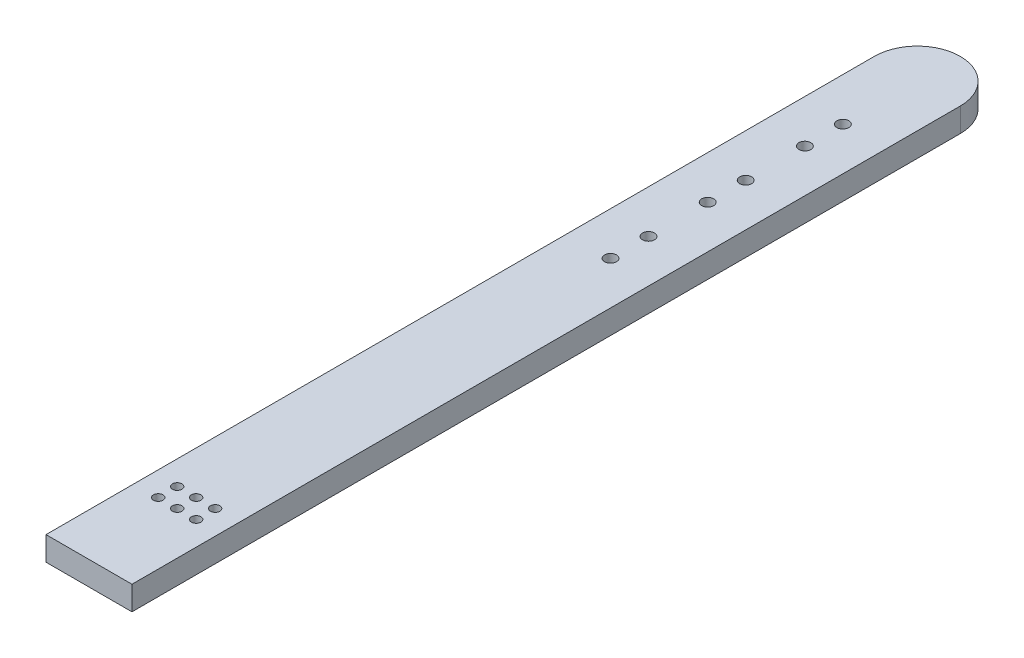
SolidWorks part; units mm, degrees
ref_plane "Front Plane" through (0, 0, 0) normal (0, 0, 1) x (1, 0, 0)
ref_plane "Top Plane" through (0, 0, 0) normal (0, 1, 0) x (1, 0, 0)
ref_plane "Right Plane" through (0, 0, 0) normal (1, 0, 0) x (0, 0, -1)
sketch "Sketch1" plane through (0, 0, 0) normal (0, 1, 0) x (1, 0, 0)
  line L0 (0, 0) -> (0, 35.2425) construction
  line L1 (-2.875, 0) -> (-2.875, 35.2425)
  line L2 (2.875, 0) -> (2.875, 35.2425)
  line L3 (-2.875, 0) -> (2.875, 0)
  line L6 (2.875, 0) -> (-2.875, 0)
  line L7 (2.875, 0) -> (2.875, -20.1575)
  line L8 (2.875, -20.1575) -> (-2.875, -20.1575)
  line L9 (-2.875, 0) -> (-2.875, -20.1575)
  line L10 (-10.6594, -20.1575) -> (-7.8276, -20.1575) construction
  arc A0 (-2.875, 0) -> (2.875, 0) centre (0, 0) ccw
  arc A1 (2.875, 35.2425) -> (-2.875, 35.2425) centre (0, 35.2425) ccw
  point P3 (0, 17.6212)
  point P10 (0, 38.1175)
  dimension "D1" = 5.75
extrude "Boss-Extrude1" add sketch "Sketch1" along normal blind 1.6 contours L2 A1 L1 L3 | A0 L9 L8 L7 | L3 A0 L6 region at (0, 0, -18.7557) region at (0, 0, 11.1963) region at (0, 0, 1.2202)
ref_axis "Axis1" through (0, 1.6, -35.2425) along (0, -1, 0)
sketch "Sketch2" plane through (0, 0, 0) normal (0, -1, 0) x (1, 0, 0)
  line L0 (-2.875, 20.1575) -> (-2.875, -35.2425) construction
  line L1 (-2.875, 20.1575) -> (-2.875, -35.2425)
  line L2 (2.875, 20.1575) -> (-2.875, 20.1575) construction
  line L3 (2.875, 20.1575) -> (-2.875, 20.1575)
  circle A0 centre (1.27, 12.9889) radius 0.3175
  circle A1 centre (0, 12.9889) radius 0.3175
  circle A2 centre (-1.27, 12.9889) radius 0.3175
  circle A3 centre (0, 14.2589) radius 0.3175
  circle A4 centre (-1.27, 14.2589) radius 0.3175
  circle A5 centre (1.27, 14.2589) radius 0.3175
  circle A6 centre (0, -30.2625) radius 0.4
  circle A10 centre (0, -23.7625) radius 0.4
  circle A11 centre (0, -17.2625) radius 0.4
  arc A12 (-2.0248, -33.6925) -> (2.0248, -33.6925) centre (0, -35.2425) ccw construction
  arc A13 (-2.875, -35.2425) -> (2.875, -35.2425) centre (0, -35.2425) ccw construction
  arc A14 (-2.875, -35.2425) -> (2.875, -35.2425) centre (0, -35.2425) ccw
  circle A15 centre (1.4441, -30.2625) radius 0.4 [skipped]
  circle A16 centre (1.4441, -23.7625) radius 0.4 [skipped]
  circle A17 centre (1.4441, -17.2625) radius 0.4 [skipped]
  circle A18 centre (0, -27.7225) radius 0.4
  circle A19 centre (0, -21.2225) radius 0.4
  circle A20 centre (0, -14.7225) radius 0.4
  point P15 (0, -35.2425)
  dimension "D1" = 0.635
  dimension "D4" = 0.8
  dimension "D7" = 4.98
  dimension "D8" = 2.875
  dimension "D9" = 55.4
  dimension "D10" = 48.2314
  dimension "D11" = 1.27
  dimension "D12" = 2.54
  dimension "D14" = 2.54
  dimension "D15" = 11.48
  dimension "D16" = 17.98
  dimension "D2" = 3
  dimension "D3" = 2
  dimension "D5" = 2
  dimension "D6" = 3
  dimension "D13" = 3
extrude "Cut-Extrude1" cut sketch "Sketch2" against normal through all contours A18 | A6 | A10 | A11 | A5 | A0 | A1 | A3 | A2 | A4 | A20 | A19
